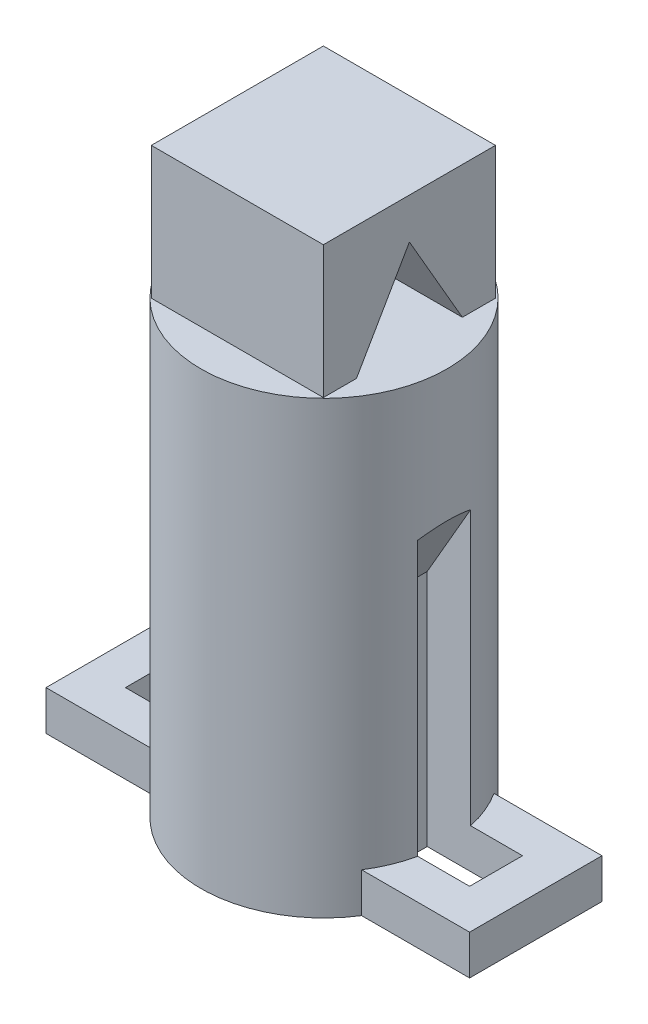
SolidWorks part; units mm, degrees
ref_plane "Front Plane" through (0, 0, 0) normal (0, 0, 1) x (1, 0, 0)
ref_plane "Top Plane" through (0, 0, 0) normal (0, 1, 0) x (1, 0, 0)
ref_plane "Right Plane" through (0, 0, 0) normal (1, 0, 0) x (0, 0, -1)
sketch "Sketch1" plane through (0, 0, 0) normal (0, 1, 0) x (1, 0, 0)
  line L1 (6.5, 6.4531) -> (-6.5, 6.4531)
  line L2 (6.5, 6.4531) -> (6.5, -6.5469)
  line L3 (6.5, -6.5469) -> (-6.5, -6.5469)
  line L4 (-6.5, 6.4531) -> (-6.5, -6.5469)
  line L5 (6.5, 6.4531) -> (-6.5, -6.5469) construction
  line L6 (6.5, -6.5469) -> (-6.5, 6.4531) construction
  dimension "D2" = 13
extrude "Boss-Extrude1" add sketch "Sketch1" along normal blind 10
sketch "Sketch2" plane through (0, 0, 0) normal (0, -1, 0) x (1, 0, 0)
  circle A0 centre (0, 0) radius 9.3
  dimension "D1" = 18.6
extrude "Boss-Extrude2" add sketch "Sketch2" along normal blind 34
sketch "Sketch3" plane through (0, -34, 0) normal (0, -1, 0) x (1, 0, 0)
  line L0 (-13, -2) -> (-13, -5) construction
  line L1 (-16, 5) -> (16, 5)
  line L2 (-16, 5) -> (-16, -5)
  line L3 (-16, -5) -> (16, -5)
  line L4 (16, 5) -> (16, -5)
  line L5 (-16, 5) -> (16, -5) construction
  line L6 (-16, -5) -> (16, 5) construction
  line L7 (-5.8, 2) -> (-13, 2)
  line L8 (-5.8, 2) -> (-5.8, -2)
  line L9 (-5.8, -2) -> (-13, -2)
  line L10 (-13, 2) -> (-13, -2)
  line L11 (-5.8, 2) -> (-13, -2) construction
  line L12 (-5.8, -2) -> (-13, 2) construction
  line L13 (-13, 2) -> (-13, 5) construction
  line L14 (0, -5.5) -> (0, 5.5) construction
  line L15 (5.8, 2) -> (13, -2) construction
  line L16 (5.8, -2) -> (13, 2) construction
  line L17 (5.8, 2) -> (5.8, -2)
  line L18 (5.8, -2) -> (13, -2)
  line L19 (5.8, 2) -> (13, 2)
  line L20 (13, 2) -> (13, -2)
  point P0 (0, 0)
  point P6 (-9.4, 0)
  point P19 (9.4, 0)
  dimension "D1" = 3
  dimension "D2" = 18.8
  dimension "D3" = 3
  dimension "D5" = 7.2
  dimension "D6" = 4
extrude "Boss-Extrude3" add sketch "Sketch3" against normal blind 3
sketch "Sketch4" plane through (-6.5, 0, 0) normal (-1, 0, 0) x (0, 0, 1)
  line L0 (-6.4531, 0) -> (6.5469, 0) construction
  line L1 (-3.9531, 0) -> (4.0469, 0)
  line L5 (-3.9531, 0) -> (-6.4531, 0) construction
  line L6 (6.5469, 0) -> (4.0469, 0) construction
  line L7 (-3.9531, 0) -> (0.0469, 6.9282)
  line L8 (0.0469, 6.9282) -> (4.0469, 0)
  dimension "D1" = 120
  dimension "D2" = 8
extrude "Cut-Extrude1" cut sketch "Sketch4" against normal through all both and the other way through all
sketch "Sketch5" plane through (0, -34, 0) normal (0, -1, 0) x (1, 0, 0)
  line L4 (-5.8, 2) -> (-13, 2)
  line L5 (-13, 2) -> (-13, -2)
  line L6 (-13, -2) -> (-5.8, -2)
  line L7 (-5.8, -2) -> (-5.8, 2)
  line L8 (-5.8, 2) -> (-13, 2)
  line L9 (-13, 2) -> (-13, -2)
  line L10 (-13, -2) -> (-5.8, -2)
  line L11 (-5.8, -2) -> (-5.8, 2)
  line L20 (5.8, -2) -> (13, -2)
  line L21 (13, -2) -> (13, 2)
  line L22 (13, 2) -> (5.8, 2)
  line L23 (5.8, 2) -> (5.8, -2)
  line L24 (5.8, -2) -> (13, -2)
  line L25 (13, -2) -> (13, 2)
  line L26 (13, 2) -> (5.8, 2)
  line L27 (5.8, 2) -> (5.8, -2)
  dimension "D1" = 0
  dimension "D3" = 0
extrude "Cut-Extrude2" cut sketch "Sketch5" against normal blind 25
chamfer "Chamfer1" distance 7 angle 30 2 edges at (-5.8, -9, 0) (5.8, -9, 0) first distance on face at (-5.8, -21.5, 0) first distance on face at (5.8, -21.5, 0)
equation "\"D1@Sketch2\"=18.6"
equation "\"D1@Boss-Extrude2\"=42.8mm - 8.8mm"
